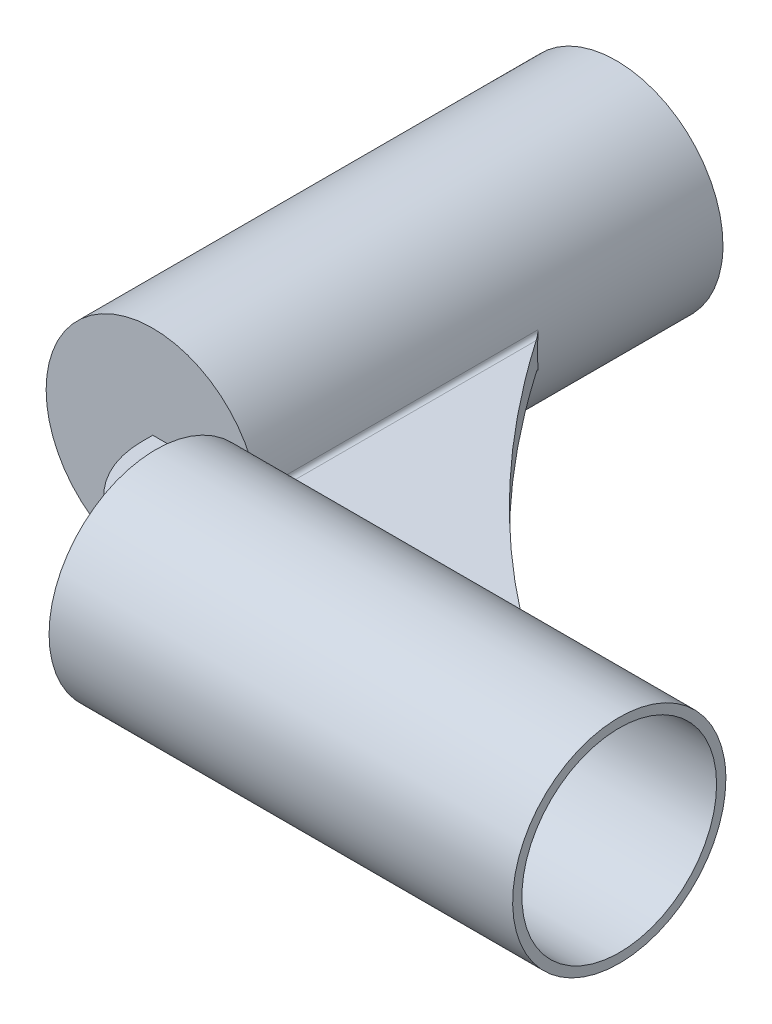
SolidWorks part; units mm, degrees
ref_plane "前视基准面" through (0, 0, 0) normal (0, 0, 1) x (1, 0, 0)
ref_plane "上视基准面" through (0, 0, 0) normal (0, 1, 0) x (1, 0, 0)
ref_plane "右视基准面" through (0, 0, 0) normal (1, 0, 0) x (0, 0, -1)
sketch "草图1" plane through (0, 0, 0) normal (0, 0, 1) x (1, 0, 0)
  circle A0 centre (0, 0) radius 11.5
  dimension "D1" = 23
extrude "凸台-拉伸1" add sketch "草图1" along normal blind 50
sketch "草图3" plane through (0, 0, 0) normal (0, 1, 0) x (1, 0, 0)
  line L0 (0, 0) -> (0, -80.2287) construction
  line L1 (0, -49.6322) -> (0, -61.1322)
  line L2 (4.1284, -61.1322) -> (18.7242, -61.1322) construction
  line L4 (0, -61.1322) -> (11.5, -61.1322)
  dimension "D1" = 11.5
  dimension "D2" = 90
  dimension "D3" = 11.5
ref_plane "基准面1" through (11.5, 0, 61.1322) normal (1, 0, 0) x (0, 0, -1)
sketch "草图4" plane through (11.5, 0, 61.1322) normal (1, 0, 0) x (0, 0, -1)
  circle A0 centre (-0.0522, 0) radius 11.5
extrude "凸台-拉伸2" add sketch "草图4" along normal blind 50 separate body
sketch "草图5" plane through (61.5, 0, 0) normal (1, 0, 0) x (0, 0, -1)
  circle A0 centre (-61.1844, 0) radius 10.5
extrude "切除-拉伸2" cut sketch "草图5" against normal blind 0.001
sketch "草图6" plane through (0, 0, 0) normal (0, 1, 0) x (1, 0, 0)
  line L0 (61.5, -61.1844) -> (0, -61.1322)
  line L1 (61.5, -71.6844) -> (61.5, -50.6844) construction
  line L2 (0, -61.1322) -> (0, 0)
  spline S0 degree 2 poles (61.5, -61.1844) (21.5929, -44.8349) (0, 0) knots 0 0 0 1 1 1
extrude "凸台-拉伸3" add sketch "草图6" along normal mid plane 3
sketch "草图2" plane through (0, 0, 0) normal (0, 0, -1) x (-1, 0, 0)
  circle A0 centre (0, 0) radius 10.5
  dimension "D1" = 21
extrude "切除-拉伸1" cut sketch "草图2" against normal blind 47
fillet "圆角1" radius 10 1 edges at (0, 0, 61.1322)
fillet "圆角2" radius 0.5 4 edges at (11.4018, 1.5, 34.927) (26.0348, 1.5, 49.7827) (26.0348, -1.5, 49.7827) (11.4018, -1.5, 34.927)
ref_plane "基准面2" through (61.5, -1.5, 61.1844) normal (1, 0, 0.0008) x (0.0008, 0, -1)
sketch "草图7" plane through (61.5, -1.5, 61.1844) normal (1, 0, 0.0008) x (0.0008, 0, -1)
sketch "草图8" plane through (61.499, 0, 0) normal (1, 0, 0) x (0, 0, -1)
  line L0 (-61.1844, 1.5) -> (-61.1844, -1.5) construction
  circle A0 centre (-61.1844, 0) radius 10.5
extrude "切除-拉伸3" cut sketch "草图8" against normal blind 47
